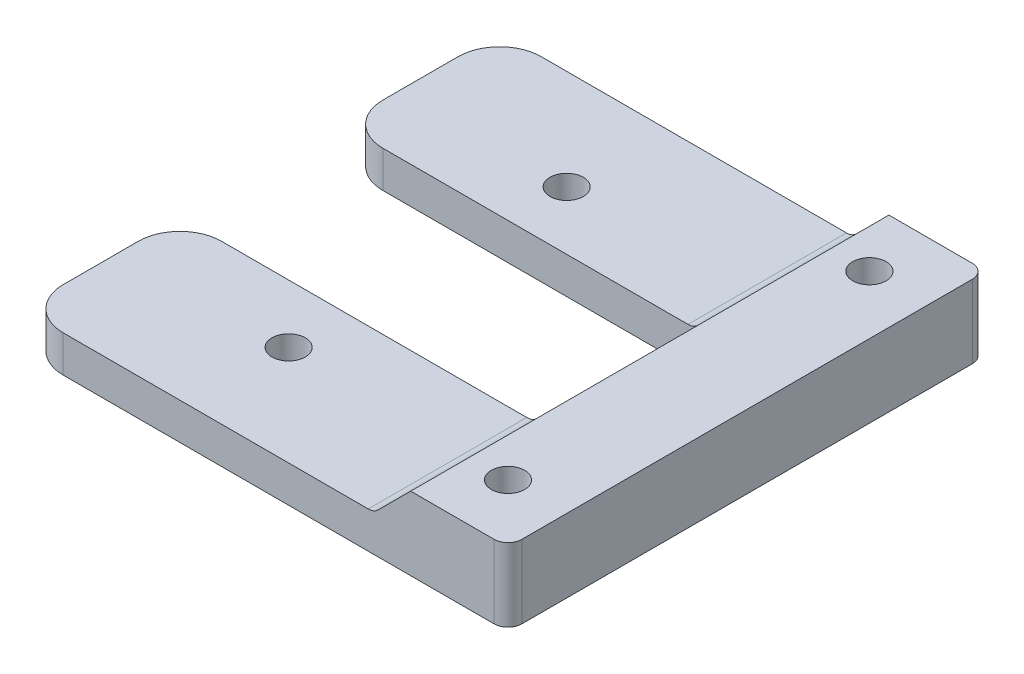
SolidWorks part; units mm, degrees
material "PLA"
ref_plane "Front Plane" through (0, 0, 0) normal (0, 0, 1) x (1, 0, 0)
ref_plane "Top Plane" through (0, 0, 0) normal (0, 1, 0) x (1, 0, 0)
ref_plane "Right Plane" through (0, 0, 0) normal (1, 0, 0) x (0, 0, -1)
sketch "Sketch1" plane through (0, 0, 0) normal (0, 0, 1) x (1, 0, 0)
  line L0 (-23, -2.635) -> (-23, -5.27) construction
  line L1 (0, 0) -> (-7, 0)
  line L2 (0, 0) -> (0, -2.635)
  line L3 (0, -2.635) -> (-7, -2.635)
  line L4 (-7, 0) -> (-7, -2.635)
  line L5 (0, -2.635) -> (-35, -2.635)
  line L6 (0, -2.635) -> (0, -5.27)
  line L7 (0, -5.27) -> (-35, -5.27)
  line L8 (-35, -2.635) -> (-35, -5.27)
  line L9 (-32, -2.635) -> (-32, -5.27) construction
  point P13 (-32, -3.9525)
  dimension "D1" = 7
  dimension "D2" = 5.27
  dimension "40" = 35
  dimension "D4" = 16
  dimension "D5" = 9
extrude "Boss-Extrude1" add sketch "Sketch1" along normal mid plane 34.4 contours L5 L8 L7 L6 L3 | L1 L4 L3 L2
sketch "Sketch2" plane through (0, 0, 0) normal (0, 1, 0) x (1, 0, 0)
  circle A0 centre (-4.2, 13) radius 1.2
  circle A1 centre (-4.2, -13) radius 1.2
  dimension "D1" = 2.4
  dimension "D2" = 13
  dimension "D3" = 13
  dimension "D4" = 4.2
extrude "Cut-Extrude1" cut sketch "Sketch2" against normal up to next
sketch "Sketch3" plane through (0, -2.635, 0) normal (0, 1, 0) x (1, 0, 0)
  line L0 (-7, -17.2) -> (-7, 17.2) construction
  line L1 (-35, -5.8) -> (-7, -5.8)
  line L2 (-35, -5.8) -> (-35, 5.8)
  line L3 (-35, 5.8) -> (-7, 5.8)
  line L4 (-7, -5.8) -> (-7, 5.8)
  line L5 (-35, -5.8) -> (-7, 5.8) construction
  line L6 (-35, 5.8) -> (-7, -5.8) construction
  line L7 (-35, -17.2) -> (-35, 17.2) construction
  circle A4 centre (-22.9798, 10) radius 1.2
  circle A5 centre (-22.9798, -10) radius 1.2
  point P0 (-21, 0)
  dimension "D1" = 2.4
  dimension "D2" = 11.6
extrude "Cut-Extrude2" cut sketch "Sketch3" against normal up to next
chamfer "Chamfer1" distance 2.635 1 edges at (-7, -2.635, -11.5)
fillet "Fillet2" radius 1 4 edges at (-7, -2.635, -5.8) (-7, -2.635, 5.8) (-9.635, -2.635, 11.5) (-9.635, -2.635, -11.5)
fillet "Fillet3" radius 3 4 edges at (-35, -3.9525, 17.2) (-35, -3.9525, 5.8) (-35, -3.9525, -5.8) (-35, -3.9525, -17.2)
fillet "Fillet4" radius 1 2 edges at (0, -2.635, 17.2) (0, -2.635, -17.2)
sketch "Sketch5" plane through (0, 0, 0) normal (0, 1, 0) x (1, 0, 0)
  line L0 (-4.2, 13) -> (-4.2, -13) construction
  point P0 (-4.2, -13)
  point P1 (-4.2, 13)
ref_plane "Plane1" through (-4.2, 0, 0) normal (1, 0, 0) x (0, 0, -1)
equation "\"D3@Sketch2\"=\"D2@Sketch2\""
